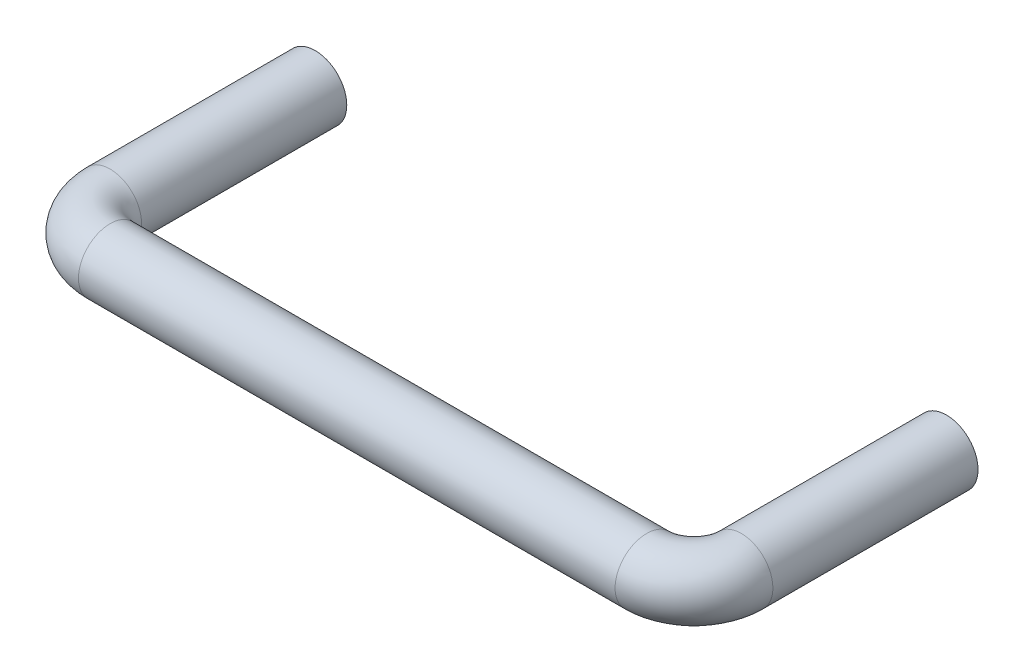
SolidWorks part; units mm, degrees
ref_plane "Front Plane" through (0, 0, 0) normal (0, 0, 1) x (1, 0, 0)
ref_plane "Top Plane" through (0, 0, 0) normal (0, 1, 0) x (1, 0, 0)
ref_plane "Right Plane" through (0, 0, 0) normal (1, 0, 0) x (0, 0, -1)
sketch "Sketch2" plane through (0, 0, 0) normal (0, 1, 0) x (1, 0, 0)
  line L0 (0, 0) -> (42.5, 0)
  line L1 (50, 7.5) -> (50, 40)
  arc A0 (50, 7.5) -> (42.5, 0) centre (42.5, 7.5) cw
  point P6 (50, 0)
  dimension "D3" = 7.5
  dimension "D1" = 50
  dimension "D2" = 40
sketch "Sketch3" plane through (0, 0, 0) normal (1, 0, 0) x (0, 0, -1)
  circle A0 centre (0, 0) radius 5
  dimension "D1" = 10
sweep "Sweep1" add profiles "Sketch3" path "Sketch2"
hole_wizard "Ø3.0 (3) Diameter Hole1" positions "Sketch4" profile "Sketch5" hole size "Ø3.0" standard "AS"
sketch "Sketch4" plane through (0, 0, -40) normal (0, 0, -1) x (-1, 0, 0)
  point P0 (-50, 0)
  point P8 (0, 0)
sketch "Sketch5" plane through (50, 0, -40) normal (1, 0, 0) x (0, 1, 0)
  line L0 (0, 0) -> (0, 10.9013)
  line L1 (0, 10.9013) -> (1.5, 10)
  line L2 (1.5, 10) -> (1.5, 0.025)
  line L3 (1.5, 0.025) -> (1.525, 0)
  line L5 (1.525, 0) -> (0, 0)
  line L6 (-1.5, 0.025) -> (-1.525, 0) construction
  line L10 (0, 10.9013) -> (-1.5, 10) construction
  line L11 (0, -6.35) -> (0, 107.95) construction
  dimension "Hole Dia." = 3
  dimension "Hole Depth" = 10
  dimension "Near C'Sink Dia." = 3.05
  dimension "Near C'Sink Angle" = 90
  dimension "Drill Angle" = 118
thread "Thread1" pitch 0.5 start angle 0, offset 0, length 0, pitch 0.5, diameter 3
ref_plane "Plane2" through (51.5, 0, -39.975) normal (0, -1, 0) x (1, 0, 0)
sketch "Thread Profile2" plane through (51.5, 0, -39.975) normal (0, -1, 0) x (1, 0, 0)
  line L0 (0, 0) -> (0, 0.5) construction
  line L1 (0, 0) -> (0.2706, 0.1562)
  line L2 (0.2706, 0.1562) -> (0.2706, 0.2187)
  line L3 (0.2706, 0.2187) -> (0, 0.375)
  line L4 (0.2706, 0.1875) -> (0, 0.1875) construction
  line L11 (0, 0) -> (0, 0.375)
  point P2 (0, 0)
  dimension "Pitch" = 0.5
  dimension "Profile_Angle" = 60
  dimension "Profile_Land" = 0.0625
  dimension "Profile_Height" = 0.2706
mirror "Mirror1" about plane through (0, 0, 0) normal (1, 0, 0) of "Thread1", "Sweep1", "Ø3.0 (3) Diameter Hole1"
